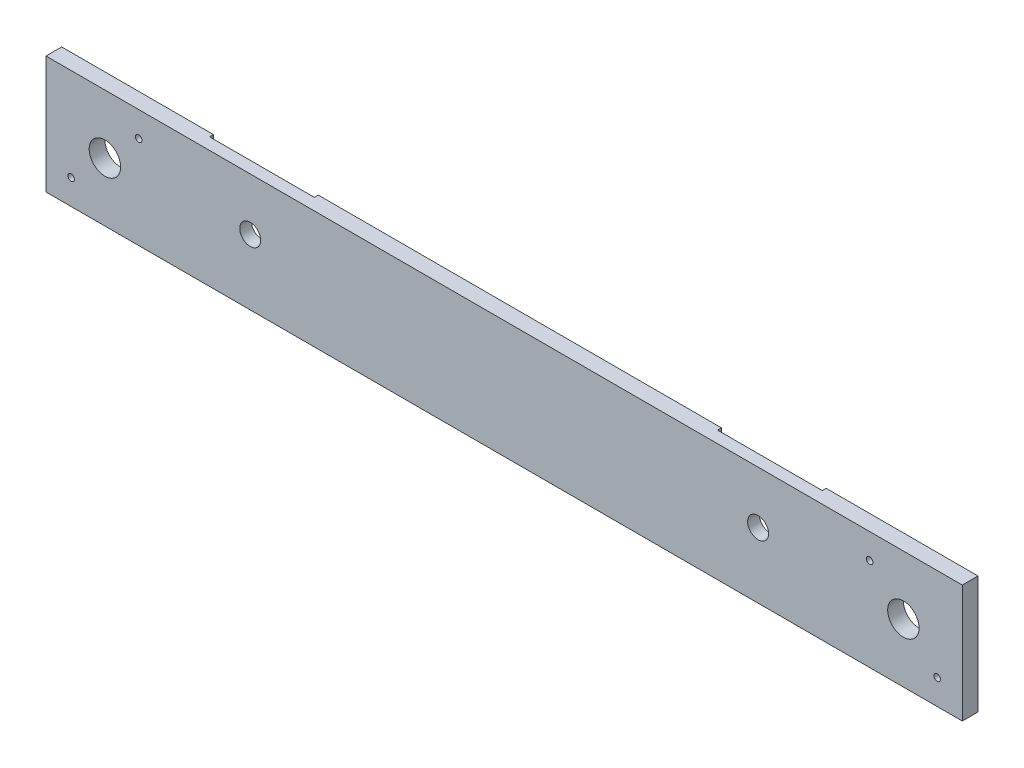
SolidWorks part; units mm, degrees
ref_plane "Alzado" through (0, 0, 0) normal (0, 0, 1) x (1, 0, 0)
ref_plane "Planta" through (0, 0, 0) normal (0, 1, 0) x (1, 0, 0)
ref_plane "Vista lateral" through (0, 0, 0) normal (1, 0, 0) x (0, 0, -1)
sketch "Croquis1" plane through (0, 0, 0) normal (0, 0, 1) x (1, 0, 0)
  line L1 (-350, -45) -> (0, -45)
  line L2 (-350, -45) -> (-350, 0)
  line L3 (-350, 0) -> (0, 0)
  line L4 (0, -45) -> (0, 0)
  dimension "D1" = 350
  dimension "D2" = 45
extrude "Saliente-Extruir1" add sketch "Croquis1" along normal blind 6 contours L3 L4 L1 L2
sketch "Croquis2" plane through (0, 0, 6) normal (0, 0, 1) x (1, 0, 0)
  line L0 (-350, -45) -> (-350, 0) construction
  line L1 (0, -45) -> (0, 0) construction
  line L2 (-350, -45) -> (0, -45) construction
  line L3 (-340.4047, -35.4047) -> (-314.5953, -9.5953) construction
  line L4 (-35.4047, -9.5953) -> (-9.5953, -35.4047) construction
  line L5 (-350, 0) -> (0, 0) construction
  circle A0 centre (-327.5, -22.5) radius 6
  circle A1 centre (-22.5, -22.5) radius 6
  circle A2 centre (-327.5, -22.5) radius 18.25 construction
  circle A4 centre (-314.5953, -9.5953) radius 1.25
  circle A5 centre (-340.4047, -35.4047) radius 1.25
  circle A6 centre (-22.5, -22.5) radius 18.25 construction
  circle A7 centre (-35.4047, -9.5953) radius 1.25
  circle A8 centre (-9.5953, -35.4047) radius 1.25
  dimension "D1" = 12
  dimension "D2" = 12
  dimension "D7" = 36.5
  dimension "D9" = 2.5
  dimension "D10" = 2.5
  dimension "D11" = 36.5
  dimension "D13" = 2.5
  dimension "D14" = 2.5
  dimension "D3" = 22.5
  dimension "D4" = 22.5
  dimension "D5" = 22.5
  dimension "D6" = 22.5
  dimension "D8" = 45
  dimension "D12" = 45
extrude "Cortar-Extruir1" cut sketch "Croquis2" against normal through all
sketch "Croquis3" plane through (0, 0, 0) normal (0, 0, 1) x (1, 0, 0)
  line L0 (-350, 0) -> (0, 0) construction
  line L1 (-98, 0) -> (-58, 0)
  line L2 (-98, 0) -> (-98, -36)
  line L3 (-94, -40) -> (-62, -40)
  line L4 (-58, 0) -> (-58, -36)
  line L5 (0, -45) -> (0, 0) construction
  line L6 (-292, 0) -> (-252, 0)
  line L7 (-292, 0) -> (-292, -36)
  line L8 (-288, -40) -> (-256, -40)
  line L9 (-252, 0) -> (-252, -36)
  line L10 (-350, -45) -> (-350, 0) construction
  arc A0 (-98, -36) -> (-94, -40) centre (-94, -36) ccw
  arc A1 (-62, -40) -> (-58, -36) centre (-62, -36) ccw
  arc A2 (-292, -36) -> (-288, -40) centre (-288, -36) ccw
  arc A3 (-256, -40) -> (-252, -36) centre (-256, -36) ccw
  point P20 (-288.6551, 0)
  point P23 (0, 0)
  dimension "D4" = 8
  dimension "D5" = 8
  dimension "D8" = 8
  dimension "D9" = 8
  dimension "D1" = 58
  dimension "D2" = 40
  dimension "D3" = 40
  dimension "D6" = 40
  dimension "D7" = 40
  dimension "D10" = 58
extrude "Cortar-Extruir4" cut sketch "Croquis3" along normal blind 1.5 from surface starting at face at (-8.3453, -35.4047, 0)
sketch "Croquis4" plane through (0, 0, 6) normal (0, 0, 1) x (1, 0, 0)
  line L0 (-350, -45) -> (-350, 0) construction
  line L1 (0, -45) -> (0, 0) construction
  line L2 (-350, 0) -> (0, 0) construction
  circle A0 centre (-272, -20) radius 4
  circle A1 centre (-78, -20) radius 4
  dimension "D1" = 8
  dimension "D2" = 8
  dimension "D3" = 78
  dimension "D4" = 78
  dimension "D5" = 20
  dimension "D6" = 20
extrude "Cortar-Extruir5" cut sketch "Croquis4" against normal through all
